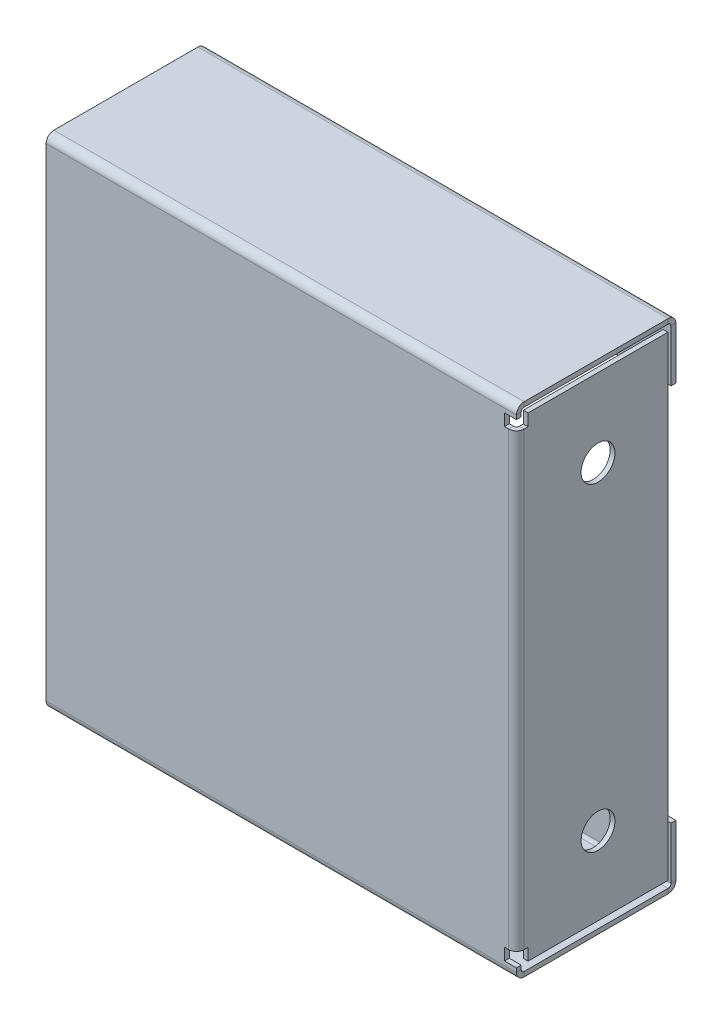
SolidWorks part; units mm, degrees
note: The reader was unsure of these and kept them because the rebuilt part matched: flange length of "Ребро-кромка2", "Ребро-кромка3", "Ребро-кромка4", "Ребро-кромка5", "Ребро-кромка6".
ref_plane "Спереди" through (0, 0, 0) normal (0, 0, 1) x (1, 0, 0)
ref_plane "Сверху" through (0, 0, 0) normal (0, 1, 0) x (1, 0, 0)
ref_plane "Справа" through (0, 0, 0) normal (1, 0, 0) x (0, 0, -1)
sketch "Эскиз1" plane through (0, 0, 0) normal (0, 0, 1) x (1, 0, 0)
  line L1 (0, 0) -> (118, 0)
  line L2 (0, 0) -> (0, 125)
  line L3 (0, 125) -> (118, 125)
  line L4 (118, 0) -> (118, 125)
  dimension "D1" = 125
  dimension "D2" = 118
base flange "Базовая кромка1" sketch "Эскиз1" thickness 1.2 reverse thickness direction no parameters "D1"=0.7366
edge flange "Ребро-кромка2" sketch "Эскиз12" flange angle 90 flange length 40 flange position material inside bend radius 0.7366 thickness 1.2 relief rectangular parameters "D6"=10
sketch "Эскиз12" plane through (0, 0, -1.2) normal (0, -1, 0) x (-1, 0, 0)
  line L0 (0, 0) -> (-118, 0) construction
  line L1 (0, 0) -> (-118, 0)
  line L2 (-118, 0) -> (-118, 38.8)
  line L3 (-118, 38.8) -> (0, 38.8)
  line L4 (0, 38.8) -> (0, 0)
bend "EdgeBend2" bend radius 0.7366 bend angle 90 parameters "D5"=1
edge flange "Ребро-кромка3" sketch "Эскиз15" flange angle 90 flange length 40 flange position material inside bend radius 0.7366 thickness 1.2 relief rectangular parameters "D6"=10
sketch "Эскиз15" plane through (0, 125, -1.2) normal (0, 1, 0) x (1, 0, 0)
  line L0 (118, 0) -> (0, 0) construction
  line L1 (118, 0) -> (0, 0)
  line L2 (0, 0) -> (0, 38.8)
  line L3 (0, 38.8) -> (118, 38.8)
  line L4 (118, 38.8) -> (118, 0)
bend "EdgeBend3" bend radius 0.7366 bend angle 90 parameters "D5"=2
edge flange "Ребро-кромка4" sketch "Эскиз18" flange angle 90 flange length 15 flange position material inside bend radius 0.7366 thickness 1.2 relief rectangular parameters "D6"=10
sketch "Эскиз18" plane through (0, 123.8, -40) normal (0, 0, -1) x (1, 0, 0)
  line L0 (118, 0) -> (0, 0) construction
  line L1 (118, 0) -> (0, 0)
  line L2 (0, 0) -> (0, 13.8)
  line L3 (0, 13.8) -> (118, 13.8)
  line L4 (118, 13.8) -> (118, 0)
bend "EdgeBend4" bend radius 0.7366 bend angle 90 parameters "D5"=3
edge flange "Ребро-кромка5" sketch "Эскиз21" flange angle 90 flange length 15 flange position material inside bend radius 0.7366 thickness 1.2 relief rectangular parameters "D6"=10
sketch "Эскиз21" plane through (0, 1.2, -40) normal (0, 0, -1) x (-1, 0, 0)
  line L0 (0, 0) -> (-118, 0) construction
  line L1 (0, 0) -> (-118, 0)
  line L2 (-118, 0) -> (-118, 13.8)
  line L3 (-118, 13.8) -> (0, 13.8)
  line L4 (0, 13.8) -> (0, 0)
bend "EdgeBend5" bend radius 0.7366 bend angle 90 parameters "D5"=4
sketch "Эскиз22" plane through (0, 0, 0) normal (0, 0, 1) x (1, 0, 0)
  line L0 (118, 0) -> (118, 125) construction
  line L1 (118, 122.0634) -> (115, 122.0634)
  line L2 (118, 122.0634) -> (118, 119.0634)
  line L3 (118, 119.0634) -> (115, 119.0634)
  line L4 (115, 122.0634) -> (115, 119.0634)
  line L5 (118, 1.9366) -> (118, 123.0634) construction
  line L6 (118, 5.9366) -> (115, 5.9366)
  line L7 (118, 5.9366) -> (118, 2.9366)
  line L8 (118, 2.9366) -> (115, 2.9366)
  line L9 (115, 5.9366) -> (115, 2.9366)
  line L11 (118, 123.0634) -> (0, 123.0634) construction
  line L12 (0, 1.9366) -> (118, 1.9366) construction
  dimension "D1" = 3
  dimension "D2" = 3
  dimension "D3" = 1
  dimension "D4" = 1
extrude "Вырез-Вытянуть2" cut sketch "Эскиз22" against normal up to next normal cut yes
edge flange "Ребро-кромка6" sketch "Эскиз25" flange angle 90 flange length 38 flange position material inside bend radius 0.7366 thickness 1.2 relief rectangular parameters "D6"=10
sketch "Эскиз25" plane through (118, 0, -1.2) normal (1, 0, 0) x (0, -1, 0)
  line L0 (-5.9366, 0) -> (-119.0634, 0) construction
  line L1 (-5.9366, 0) -> (-119.0634, 0)
  line L2 (-119.0634, 0) -> (-119.0634, 36.8)
  line L3 (-119.0634, 36.8) -> (-5.9366, 36.8)
  line L4 (-5.9366, 36.8) -> (-5.9366, 0)
bend "EdgeBend6" bend radius 0.7366 bend angle 90 parameters "D5"=5
sketch "Эскиз26" plane through (118, 0, 0) normal (1, 0, 0) x (0, 0, -1)
  line L0 (1.9366, 5.9366) -> (1.9366, 119.0634) construction
  line L1 (38, 119.0634) -> (2.9366, 119.0634)
  line L2 (38, 119.0634) -> (38, 122.0634)
  line L3 (38, 122.0634) -> (2.9366, 122.0634)
  line L4 (2.9366, 119.0634) -> (2.9366, 122.0634)
  line L5 (38, 5.9366) -> (2.9366, 5.9366)
  line L6 (38, 5.9366) -> (38, 2.9366)
  line L7 (38, 2.9366) -> (2.9366, 2.9366)
  line L8 (2.9366, 5.9366) -> (2.9366, 2.9366)
  dimension "D1" = 1
  dimension "D2" = 3
extrude "Бобышка-Вытянуть1" add sketch "Эскиз26" against normal up to surface (1.2 mm away) up to face at (116.8, 62.5, -19.9683)
sketch "Эскиз27" plane through (118, 0, 0) normal (1, 0, 0) x (0, 0, -1)
  line L0 (20.4683, 122.0634) -> (20.4683, 2.9366) construction
  line L1 (38, 122.0634) -> (2.9366, 122.0634) construction
  line L2 (2.9366, 2.9366) -> (38, 2.9366) construction
  line L3 (1.9366, 62.5) -> (38, 62.5) construction
  line L4 (1.9366, 5.9366) -> (1.9366, 119.0634) construction
  line L5 (38, 2.9366) -> (38, 122.0634) construction
  circle A0 centre (20.4683, 102.5) radius 4.25
  circle A1 centre (20.4683, 22.5) radius 4.25
  dimension "D1" = 80
  dimension "D2" = 40
  dimension "D3" = 8.5
extrude "Вырез-Вытянуть3" cut sketch "Эскиз27" against normal up to next normal cut yes
sketch "Эскиз28" plane through (0, 0, -40) normal (0, 0, -1) x (-1, 0, 0)
  line L0 (-56, 118.4683) -> (-80, 118.4683) construction
  line L1 (-56, 6.5317) -> (-80, 6.5317) construction
  line L2 (-80, 118.4683) -> (-80, 6.5317) construction
  line L4 (-56, 118.4683) -> (-56, 6.5317) construction
  line L5 (-118, 123.0634) -> (-118, 110) construction
  line L9 (-118, 110) -> (0, 110) construction
  line L10 (0, 15) -> (-118, 15) construction
  circle A0 centre (-80, 118.4683) radius 2.25
  circle A1 centre (-56, 118.4683) radius 2.25
  circle A2 centre (-80, 6.5317) radius 2.25
  circle A3 centre (-56, 6.5317) radius 2.25
  dimension "D5" = 4.5
  dimension "D1" = 38
  dimension "D2" = 24
  dimension "D3" = 8.4683
  dimension "D4" = 8.4683
extrude "Вырез-Вытянуть4" cut sketch "Эскиз28" against normal up to next normal cut yes
sketch "Эскиз29" plane through (0, 0, -40) normal (0, 0, -1) x (-1, 0, 0)
  line L0 (-12, 117) -> (-32, 117) construction
  line L1 (-32, 117) -> (-32, 8) construction
  line L2 (-32, 8) -> (-12, 8) construction
  line L3 (0, 123.0634) -> (0, 1.9366) construction
  line L4 (-12, 117) -> (-12, 8) construction
  line L5 (-118, 110) -> (0, 110) construction
  line L6 (0, 15) -> (-118, 15) construction
  circle A1 centre (-32, 117) radius 2.25
  circle A2 centre (-12, 117) radius 2.25
  circle A3 centre (-32, 8) radius 2.25
  circle A4 centre (-12, 8) radius 2.25
  dimension "D5" = 4.5
  dimension "D1" = 12
  dimension "D2" = 20
  dimension "D3" = 7
  dimension "D4" = 7
extrude "Вырез-Вытянуть5" cut sketch "Эскиз29" against normal up to next normal cut yes
sketch "Сгиб-Линии1" plane through (0, 0, 0) normal (0, 1, 0) x (1, 0, 0)
sketch "Граничная рамка1" plane through (0, 0, 0) normal (0, 1, 0) x (1, 0, 0)
sheet metal parameters "Листовой металл3" thickness 1.2 parameters "D1"=0.7366
flat pattern "Развертка3" [suppressed]
sketch "Сгиб-Линии2" plane through (0, 0, 0) normal (0, 1, 0) x (1, 0, 0)
sketch "Граничная рамка2" [suppressed] plane through (0, 0, 0) normal (0, 1, 0) x (1, 0, 0)
sheet metal parameters "Листовой металл6" thickness 1.2 parameters "D1"=0.7366
flat pattern "Развертка3" [suppressed]
sketch "Сгиб-Линии2" plane through (0, 0, 0) normal (0, 1, 0) x (1, 0, 0)
sketch "Граничная рамка2" [suppressed] plane through (0, 0, 0) normal (0, 1, 0) x (1, 0, 0)
bend of the flat pattern "Плоское состояние-<EdgeBend2>1"
sheet metal parameters "Листовой металл7" thickness 1.2 parameters "D1"=0.7366
flat pattern "Развертка3" [suppressed]
sketch "Сгиб-Линии2" plane through (0, 0, 0) normal (0, 1, 0) x (1, 0, 0)
sketch "Граничная рамка2" [suppressed] plane through (0, 0, 0) normal (0, 1, 0) x (1, 0, 0)
bend of the flat pattern "Плоское состояние-<EdgeBend2>1"
bend of the flat pattern "Плоское состояние-<EdgeBend3>1"
sheet metal parameters "Листовой металл8" thickness 1.2 parameters "D1"=0.7366
flat pattern "Развертка3" [suppressed]
sketch "Сгиб-Линии2" plane through (0, 0, 0) normal (0, 1, 0) x (1, 0, 0)
sketch "Граничная рамка2" [suppressed] plane through (0, 0, 0) normal (0, 1, 0) x (1, 0, 0)
bend of the flat pattern "Плоское состояние-<EdgeBend2>1"
bend of the flat pattern "Плоское состояние-<EdgeBend3>1"
bend of the flat pattern "Плоское состояние-<EdgeBend4>1"
sheet metal parameters "Листовой металл9" thickness 1.2 parameters "D1"=0.7366
flat pattern "Развертка3" [suppressed]
sketch "Сгиб-Линии2" plane through (0, 0, 0) normal (0, 1, 0) x (1, 0, 0)
sketch "Граничная рамка2" [suppressed] plane through (0, 0, 0) normal (0, 1, 0) x (1, 0, 0)
bend of the flat pattern "Плоское состояние-<EdgeBend2>1"
bend of the flat pattern "Плоское состояние-<EdgeBend3>1"
bend of the flat pattern "Плоское состояние-<EdgeBend4>1"
bend of the flat pattern "Плоское состояние-<EdgeBend5>1"
sheet metal parameters "Листовой металл10" thickness 1.2 parameters "D1"=0.7366
flat pattern "Развертка3" [suppressed]
sketch "Сгиб-Линии2" plane through (0, 0, 0) normal (0, 1, 0) x (1, 0, 0)
sketch "Граничная рамка2" [suppressed] plane through (0, 0, 0) normal (0, 1, 0) x (1, 0, 0)
bend of the flat pattern "Плоское состояние-<EdgeBend2>1"
bend of the flat pattern "Плоское состояние-<EdgeBend3>1"
bend of the flat pattern "Плоское состояние-<EdgeBend4>1"
bend of the flat pattern "Плоское состояние-<EdgeBend5>1"
sheet metal parameters "Листовой металл11" thickness 1.2 parameters "D1"=0.7366
flat pattern "Развертка3" [suppressed]
sketch "Сгиб-Линии2" plane through (0, 0, 0) normal (0, 1, 0) x (1, 0, 0)
sketch "Граничная рамка2" [suppressed] plane through (0, 0, 0) normal (0, 1, 0) x (1, 0, 0)
bend of the flat pattern "Плоское состояние-<EdgeBend2>1"
bend of the flat pattern "Плоское состояние-<EdgeBend3>1"
bend of the flat pattern "Плоское состояние-<EdgeBend4>1"
bend of the flat pattern "Плоское состояние-<EdgeBend5>1"
bend of the flat pattern "Плоское состояние-<EdgeBend6>1"
sheet metal parameters "Листовой металл12" thickness 1.2 parameters "D1"=0.7366
flat pattern "Развертка3" [suppressed]
sketch "Сгиб-Линии2" plane through (0, 0, 0) normal (0, 1, 0) x (1, 0, 0)
sketch "Граничная рамка2" [suppressed] plane through (0, 0, 0) normal (0, 1, 0) x (1, 0, 0)
bend of the flat pattern "Плоское состояние-<EdgeBend2>1"
bend of the flat pattern "Плоское состояние-<EdgeBend3>1"
bend of the flat pattern "Плоское состояние-<EdgeBend4>1"
bend of the flat pattern "Плоское состояние-<EdgeBend5>1"
bend of the flat pattern "Плоское состояние-<EdgeBend6>1"
sheet metal parameters "Листовой металл13" thickness 1.2 parameters "D1"=0.7366
flat pattern "Развертка3" [suppressed]
sketch "Сгиб-Линии2" plane through (0, 0, 0) normal (0, 1, 0) x (1, 0, 0)
sketch "Граничная рамка2" [suppressed] plane through (0, 0, 0) normal (0, 1, 0) x (1, 0, 0)
bend of the flat pattern "Плоское состояние-<EdgeBend2>1"
bend of the flat pattern "Плоское состояние-<EdgeBend3>1"
bend of the flat pattern "Плоское состояние-<EdgeBend4>1"
bend of the flat pattern "Плоское состояние-<EdgeBend5>1"
bend of the flat pattern "Плоское состояние-<EdgeBend6>1"
sheet metal parameters "Листовой металл14" thickness 1.2 parameters "D1"=0.7366
flat pattern "Развертка3" [suppressed]
sketch "Сгиб-Линии2" plane through (0, 0, 0) normal (0, 1, 0) x (1, 0, 0)
sketch "Граничная рамка2" [suppressed] plane through (0, 0, 0) normal (0, 1, 0) x (1, 0, 0)
bend of the flat pattern "Плоское состояние-<EdgeBend2>1"
bend of the flat pattern "Плоское состояние-<EdgeBend3>1"
bend of the flat pattern "Плоское состояние-<EdgeBend4>1"
bend of the flat pattern "Плоское состояние-<EdgeBend5>1"
bend of the flat pattern "Плоское состояние-<EdgeBend6>1"
sheet metal parameters "Листовой металл15" thickness 1.2 parameters "D1"=0.7366
flat pattern "Развертка3" [suppressed]
sketch "Сгиб-Линии2" plane through (0, 0, 0) normal (0, 1, 0) x (1, 0, 0)
sketch "Граничная рамка2" [suppressed] plane through (0, 0, 0) normal (0, 1, 0) x (1, 0, 0)
bend of the flat pattern "Плоское состояние-<EdgeBend2>1"
bend of the flat pattern "Плоское состояние-<EdgeBend3>1"
bend of the flat pattern "Плоское состояние-<EdgeBend4>1"
bend of the flat pattern "Плоское состояние-<EdgeBend5>1"
bend of the flat pattern "Плоское состояние-<EdgeBend6>1"
